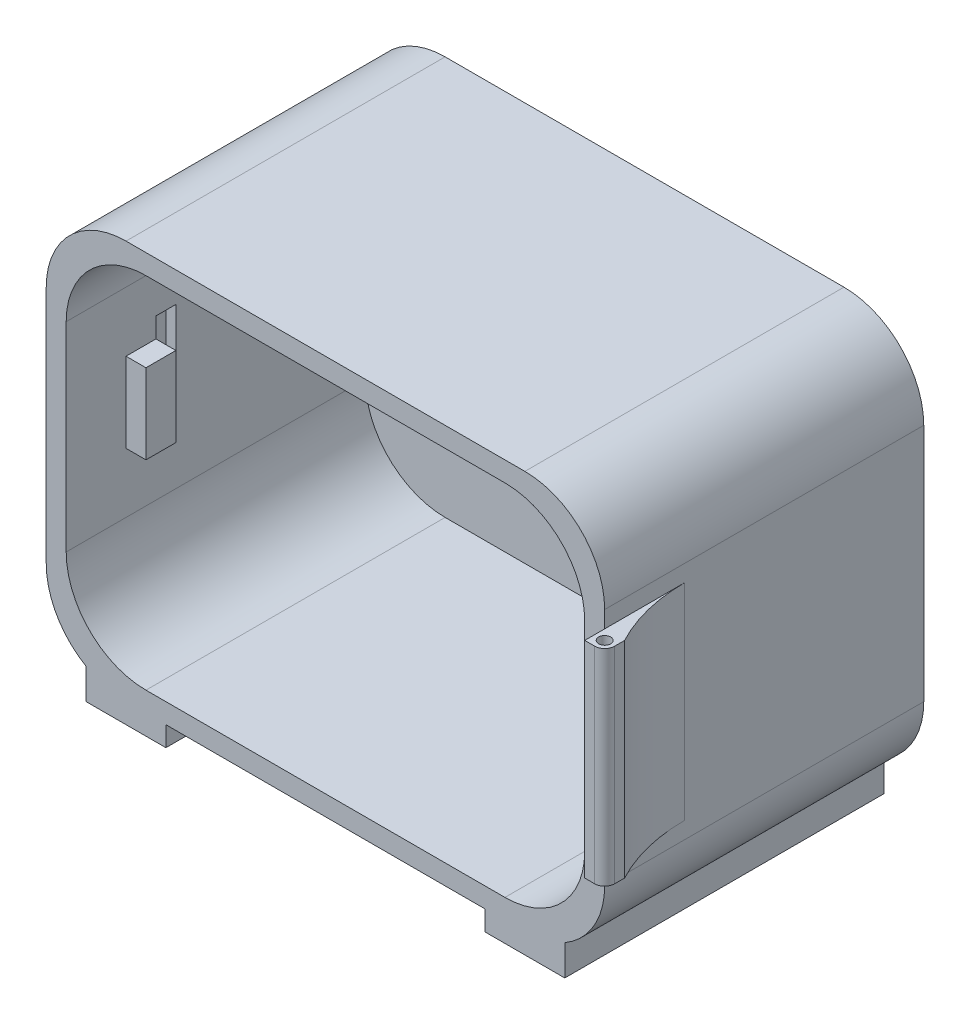
SolidWorks part; units mm, degrees
ref_plane "Front Plane" through (0, 0, 0) normal (0, 0, 1) x (1, 0, 0)
ref_plane "Top Plane" through (0, 0, 0) normal (0, 1, 0) x (1, 0, 0)
ref_plane "Right Plane" through (0, 0, 0) normal (1, 0, 0) x (0, 0, -1)
sketch "Sketch1" plane through (0, 0, 0) normal (0, 0, 1) x (1, 0, 0)
  line L0 (-82.55, 31.75) -> (-82.55, -31.75)
  line L1 (-63.5, 63.5) -> (63.5, 63.5)
  line L2 (-88.9, 38.1) -> (-88.9, -38.1)
  line L3 (-63.5, -63.5) -> (63.5, -63.5)
  line L4 (88.9, 38.1) -> (88.9, -38.1)
  line L5 (-88.9, 63.5) -> (88.9, -63.5) construction
  line L6 (-88.9, -63.5) -> (88.9, 63.5) construction
  line L7 (-57.15, -57.15) -> (57.15, -57.15)
  line L8 (82.55, 31.75) -> (82.55, -31.75)
  line L9 (-57.15, 57.15) -> (57.15, 57.15)
  line L10 (-88.9, 63.5) -> (88.9, 63.5) construction
  line L11 (88.9, 63.5) -> (88.9, -63.5) construction
  line L12 (82.55, 57.15) -> (82.55, -57.15) construction
  line L13 (-82.55, 57.15) -> (82.55, 57.15) construction
  line L14 (-82.55, -57.15) -> (82.55, -57.15) construction
  line L15 (-88.9, -63.5) -> (88.9, -63.5) construction
  line L16 (-82.55, 57.15) -> (-82.55, -57.15) construction
  line L17 (-88.9, 63.5) -> (-88.9, -63.5) construction
  arc A0 (63.5, 63.5) -> (88.9, 38.1) centre (63.5, 38.1) cw
  arc A1 (82.55, 31.75) -> (57.15, 57.15) centre (57.15, 31.75) ccw
  arc A2 (57.15, -57.15) -> (82.55, -31.75) centre (57.15, -31.75) ccw
  arc A3 (63.5, -63.5) -> (88.9, -38.1) centre (63.5, -38.1) ccw
  arc A4 (-82.55, -31.75) -> (-57.15, -57.15) centre (-57.15, -31.75) ccw
  arc A5 (-88.9, -38.1) -> (-63.5, -63.5) centre (-63.5, -38.1) ccw
  arc A6 (-63.5, 63.5) -> (-88.9, 38.1) centre (-63.5, 38.1) ccw
  arc A7 (-82.55, 31.75) -> (-57.15, 57.15) centre (-57.15, 31.75) cw
  point P0 (0, 0)
  dimension "D4" = 25.4
  dimension "D1" = 177.8
  dimension "D2" = 127
  dimension "D3" = 6.35
extrude "Boss-Extrude1" add sketch "Sketch1" against normal blind 95.25
sketch "Sketch2" plane through (0, 0, -95.25) normal (0, 0, -1) x (-1, 0, 0)
  line L0 (-63.5, 63.5) -> (63.5, 63.5)
  line L1 (-63.5, 63.5) -> (63.5, 63.5) construction
  line L2 (0, 63.5) -> (0, -63.5) construction
  line L3 (63.5, -63.5) -> (-63.5, -63.5) construction
  line L4 (63.5, -63.5) -> (-63.5, -63.5)
  line L5 (-88.9, -38.1) -> (-88.9, 38.1) construction
  line L6 (-88.9, -38.1) -> (-88.9, 38.1)
  line L7 (88.9, -38.1) -> (88.9, 38.1)
  arc A0 (-88.9, 38.1) -> (-63.5, 63.5) centre (-63.5, 38.1) cw
  arc A1 (-63.5, -63.5) -> (-88.9, -38.1) centre (-63.5, -38.1) cw
  arc A2 (-88.9, -38.1) -> (-63.5, -63.5) centre (-63.5, -38.1) ccw construction
  arc A3 (63.5, -63.5) -> (88.9, -38.1) centre (63.5, -38.1) ccw
  arc A4 (88.9, 38.1) -> (63.5, 63.5) centre (63.5, 38.1) ccw
extrude "Boss-Extrude2" add sketch "Sketch2" along normal blind 6.35
sketch "Sketch4" plane through (0, -63.5, 0) normal (0, -1, 0) x (1, 0, 0)
  line L0 (-76.2, 0) -> (-50.8, 0)
  line L2 (-76.2, 0) -> (-76.2, -101.6)
  line L3 (-88.9, -101.6) -> (-63.5, -101.6) construction
  line L4 (-76.2, -101.6) -> (-50.8, -101.6)
  line L5 (63.5, -101.6) -> (-63.5, -101.6) construction
  line L6 (-50.8, -101.6) -> (-50.8, 0)
  line L7 (0, 0) -> (0, -101.6) construction
  line L8 (-63.5, 0) -> (63.5, 0) construction
  line L9 (76.2, -101.6) -> (50.8, -101.6)
  line L10 (76.2, 0) -> (76.2, -101.6)
  line L11 (76.2, 0) -> (50.8, 0)
  line L12 (50.8, -101.6) -> (50.8, 0)
  point P4 (-63.5, 0)
  dimension "D1" = 25.4
extrude "Boss-Extrude3" add sketch "Sketch4" along normal blind 6.35 and the other way up to next
sketch "Sketch5" plane through (0, 0, 0) normal (0, 1, 0) x (1, 0, 0)
  line L0 (0, 0) -> (88.9, 0) construction
  line L1 (63.5, 0) -> (-63.5, 0) construction
  line L2 (92.075, 0) -> (95.25, 0) construction
  line L3 (88.9, 25.4) -> (88.9, 0)
  line L4 (92.075, 0) -> (92.075, -3.175) construction
  line L7 (95.25, -6.35) -> (88.9, -6.35)
  line L8 (95.25, -6.35) -> (95.25, 0)
  line L9 (95.25, 0) -> (92.075, 0)
  line L10 (88.9, -6.35) -> (88.9, 0)
  line L11 (95.25, -6.35) -> (88.9, 0) construction
  line L12 (95.25, 0) -> (88.9, -6.35) construction
  line L13 (88.9, -3.175) -> (95.25, -3.175) construction
  arc A3 (95.25, 0) -> (88.9, 25.4) centre (142.875, 25.4) cw
  circle A4 centre (92.075, -3.175) radius 1.905
  point P4 (93.6625, 0)
  dimension "D2" = 3.81
  dimension "D1" = 3.175
  dimension "D3" = 88.9
  dimension "D4" = 25.4
extrude "Boss-Extrude5" add sketch "Sketch5" along normal blind 32.766 and the other way blind 32.766 contours A3 L3 L10 L7 L8 A4 region at (91.243, 0, -2.9141)
fillet "Fillet1" radius 3.175 1 edges at (95.25, 0, 6.35)
sketch "Sketch6" plane through (0, 32.766, 0) normal (0, 1, 0) x (1, 0, 0)
  line L0 (90.17, -3.175) -> (88.9, -3.175) construction
  line L1 (88.9, 0) -> (88.9, -6.35) construction
  line L2 (93.98, -3.175) -> (95.25, -3.175) construction
  circle A0 centre (92.075, -3.175) radius 1.905 construction
sketch "Sketch8" plane through (-82.55, 0, 0) normal (1, 0, 0) x (0, 0, -1)
  line L0 (0, -19.05) -> (28.575, -19.05) construction
  line L1 (0, 31.75) -> (0, -31.75) construction
  line L2 (28.575, -19.05) -> (34.925, -19.05)
  line L3 (34.925, -19.05) -> (34.925, 19.05)
  line L4 (34.925, 19.05) -> (28.575, 19.05)
  line L5 (28.575, 19.05) -> (28.575, -19.05)
  line L6 (95.25, -57.15) -> (0, -57.15) construction
  point P2 (0, 0)
  point P3 (0, 0)
  point P4 (6.4557, 0)
  point P9 (0, 0)
  point P10 (0, 0)
  dimension "D1" = 28.575
  dimension "D2" = 6.35
  dimension "D3" = 38.1
  dimension "D4" = 38.1
extrude "Cut-Extrude1" cut sketch "Sketch8" against normal blind 3.175
sketch "Sketch10" plane through (-82.55, 0, 0) normal (1, 0, 0) x (0, 0, -1)
  line L0 (28.575, 0) -> (28.575, 12.7) construction
  line L1 (28.575, 19.05) -> (28.575, -19.05) construction
  line L3 (28.575, 12.7) -> (19.05, 12.7)
  line L4 (28.575, 12.7) -> (28.575, -12.7)
  line L5 (28.575, -12.7) -> (19.05, -12.7)
  line L6 (19.05, 12.7) -> (19.05, -12.7)
  point P7 (28.575, 0)
  dimension "D1" = 12.7
  dimension "D2" = 9.525
extrude "Boss-Extrude6" add sketch "Sketch10" along normal blind 6.35
